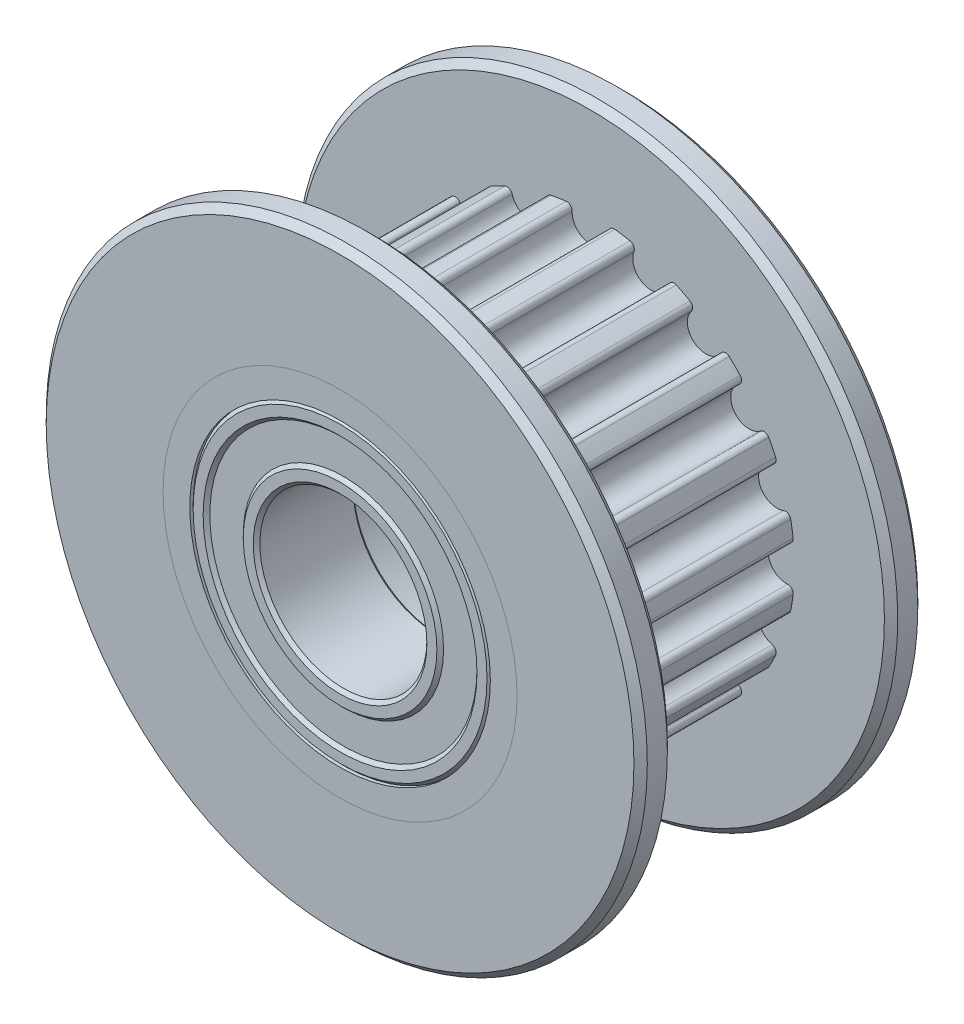
SolidWorks part; units mm, degrees
ref_plane "Přední rovina" through (0, 0, 0) normal (0, 0, 1) x (1, 0, 0)
ref_plane "Horní rovina" through (0, 0, 0) normal (0, 1, 0) x (1, 0, 0)
ref_plane "Pravá rovina" through (0, 0, 0) normal (1, 0, 0) x (0, 0, -1)
sketch "Skica1" plane through (0, 0, 0) normal (0, 0, 1) x (1, 0, 0)
  circle A0 centre (0, 0) radius 5.3
  circle A1 centre (0, 0) radius 4
  circle A2 centre (0, 0) radius 9
  dimension "D1" = 10.6
  dimension "D2" = 8
  dimension "D3" = 18
extrude "Přidat vysunutím1" add sketch "Skica1" along normal blind 8.5 contours A0 A1 region at (-5.1501, 0, 0)
extrude "Přidat vysunutím2" add sketch "Skica1<3>" along normal blind 1 separate body contours A2 A0 region at (-8.7454, 0, 0)
sketch "Skica1<3>" plane through (0, 0, 0) normal (0, 0, 1) x (1, 0, 0) same geometry as "Skica1"
sketch "Skica2" plane through (0, 0, 1) normal (0, 0, 1) x (1, 0, 0)
  arc A2 (-0.5492, 5.8991) -> (0.5492, 5.8991) centre (0, 5.87) ccw
  arc A3 (-0.5492, 5.8991) -> (-0.7281, 6.0665) centre (-0.709, 5.9076) ccw
  arc A4 (0.7281, 6.0665) -> (0.5492, 5.8991) centre (0.709, 5.9076) ccw
  arc A5 (1.1822, 5.9945) -> (0.7281, 6.0665) centre (0, 0) ccw
  arc A6 (1.3006, 5.7801) -> (2.3453, 5.4407) centre (1.8139, 5.5827) ccw
  arc A7 (1.3006, 5.7801) -> (1.1822, 5.9945) centre (1.1512, 5.8376) ccw
  arc A8 (2.5671, 5.5446) -> (2.3453, 5.4407) centre (2.4999, 5.3994) ccw
  arc A9 (2.9768, 5.3358) -> (2.5671, 5.5446) centre (0, 0) ccw
  arc A10 (3.0231, 5.0953) -> (3.9118, 4.4497) centre (3.4503, 4.7489) ccw
  arc A11 (3.0231, 5.0953) -> (2.9768, 5.3358) centre (2.8988, 5.1961) ccw
  arc A12 (4.1548, 4.4799) -> (3.9118, 4.4497) centre (4.046, 4.3626) ccw
  arc A13 (4.4799, 4.1548) -> (4.1548, 4.4799) centre (0, 0) ccw
  arc A14 (4.4497, 3.9118) -> (5.0953, 3.0231) centre (4.7489, 3.4503) ccw
  arc A15 (4.4497, 3.9118) -> (4.4799, 4.1548) centre (4.3626, 4.046) ccw
  arc A16 (5.3358, 2.9768) -> (5.0953, 3.0231) centre (5.1961, 2.8988) ccw
  arc A17 (5.5446, 2.5671) -> (5.3358, 2.9768) centre (0, 0) ccw
  arc A18 (5.4407, 2.3453) -> (5.7801, 1.3006) centre (5.5827, 1.8139) ccw
  arc A19 (5.4407, 2.3453) -> (5.5446, 2.5671) centre (5.3994, 2.4999) ccw
  arc A20 (5.9945, 1.1822) -> (5.7801, 1.3006) centre (5.8376, 1.1512) ccw
  arc A21 (6.0665, 0.7281) -> (5.9945, 1.1822) centre (0, 0) ccw
  arc A22 (5.8991, 0.5492) -> (5.8991, -0.5492) centre (5.87, 0) ccw
  arc A23 (5.8991, 0.5492) -> (6.0665, 0.7281) centre (5.9076, 0.709) ccw
  arc A24 (6.0665, -0.7281) -> (5.8991, -0.5492) centre (5.9076, -0.709) ccw
  arc A25 (5.9945, -1.1822) -> (6.0665, -0.7281) centre (0, 0) ccw
  arc A26 (5.7801, -1.3006) -> (5.4407, -2.3453) centre (5.5827, -1.8139) ccw
  arc A27 (5.7801, -1.3006) -> (5.9945, -1.1822) centre (5.8376, -1.1512) ccw
  arc A28 (5.5446, -2.5671) -> (5.4407, -2.3453) centre (5.3994, -2.4999) ccw
  arc A29 (5.3358, -2.9768) -> (5.5446, -2.5671) centre (0, 0) ccw
  arc A30 (5.0953, -3.0231) -> (4.4497, -3.9118) centre (4.7489, -3.4503) ccw
  arc A31 (5.0953, -3.0231) -> (5.3358, -2.9768) centre (5.1961, -2.8988) ccw
  arc A32 (4.4799, -4.1548) -> (4.4497, -3.9118) centre (4.3626, -4.046) ccw
  arc A33 (4.1548, -4.4799) -> (4.4799, -4.1548) centre (0, 0) ccw
  arc A34 (3.9118, -4.4497) -> (3.0231, -5.0953) centre (3.4503, -4.7489) ccw
  arc A35 (3.9118, -4.4497) -> (4.1548, -4.4799) centre (4.046, -4.3626) ccw
  arc A36 (2.9768, -5.3358) -> (3.0231, -5.0953) centre (2.8988, -5.1961) ccw
  arc A37 (2.5671, -5.5446) -> (2.9768, -5.3358) centre (0, 0) ccw
  arc A38 (2.3453, -5.4407) -> (1.3006, -5.7801) centre (1.8139, -5.5827) ccw
  arc A39 (2.3453, -5.4407) -> (2.5671, -5.5446) centre (2.4999, -5.3994) ccw
  arc A40 (1.1822, -5.9945) -> (1.3006, -5.7801) centre (1.1512, -5.8376) ccw
  arc A41 (0.7281, -6.0665) -> (1.1822, -5.9945) centre (0, 0) ccw
  arc A42 (0.5492, -5.8991) -> (-0.5492, -5.8991) centre (0, -5.87) ccw
  arc A43 (0.5492, -5.8991) -> (0.7281, -6.0665) centre (0.709, -5.9076) ccw
  arc A44 (-0.7281, -6.0665) -> (-0.5492, -5.8991) centre (-0.709, -5.9076) ccw
  arc A45 (-1.1822, -5.9945) -> (-0.7281, -6.0665) centre (0, 0) ccw
  arc A46 (-1.3006, -5.7801) -> (-2.3453, -5.4407) centre (-1.8139, -5.5827) ccw
  arc A47 (-1.3006, -5.7801) -> (-1.1822, -5.9945) centre (-1.1512, -5.8376) ccw
  arc A48 (-2.5671, -5.5446) -> (-2.3453, -5.4407) centre (-2.4999, -5.3994) ccw
  arc A49 (-2.9768, -5.3358) -> (-2.5671, -5.5446) centre (0, 0) ccw
  arc A50 (-3.0231, -5.0953) -> (-3.9118, -4.4497) centre (-3.4503, -4.7489) ccw
  arc A51 (-3.0231, -5.0953) -> (-2.9768, -5.3358) centre (-2.8988, -5.1961) ccw
  arc A52 (-4.1548, -4.4799) -> (-3.9118, -4.4497) centre (-4.046, -4.3626) ccw
  arc A53 (-4.4799, -4.1548) -> (-4.1548, -4.4799) centre (0, 0) ccw
  arc A54 (-4.4497, -3.9118) -> (-5.0953, -3.0231) centre (-4.7489, -3.4503) ccw
  arc A55 (-4.4497, -3.9118) -> (-4.4799, -4.1548) centre (-4.3626, -4.046) ccw
  arc A56 (-5.3358, -2.9768) -> (-5.0953, -3.0231) centre (-5.1961, -2.8988) ccw
  arc A57 (-5.5446, -2.5671) -> (-5.3358, -2.9768) centre (0, 0) ccw
  arc A58 (-5.4407, -2.3453) -> (-5.7801, -1.3006) centre (-5.5827, -1.8139) ccw
  arc A59 (-5.4407, -2.3453) -> (-5.5446, -2.5671) centre (-5.3994, -2.4999) ccw
  arc A60 (-5.9945, -1.1822) -> (-5.7801, -1.3006) centre (-5.8376, -1.1512) ccw
  arc A61 (-6.0665, -0.7281) -> (-5.9945, -1.1822) centre (0, 0) ccw
  arc A62 (-5.8991, -0.5492) -> (-5.8991, 0.5492) centre (-5.87, 0) ccw
  arc A63 (-5.8991, -0.5492) -> (-6.0665, -0.7281) centre (-5.9076, -0.709) ccw
  arc A64 (-6.0665, 0.7281) -> (-5.8991, 0.5492) centre (-5.9076, 0.709) ccw
  arc A65 (-5.9945, 1.1822) -> (-6.0665, 0.7281) centre (0, 0) ccw
  arc A66 (-5.7801, 1.3006) -> (-5.4407, 2.3453) centre (-5.5827, 1.8139) ccw
  arc A67 (-5.7801, 1.3006) -> (-5.9945, 1.1822) centre (-5.8376, 1.1512) ccw
  arc A68 (-5.5446, 2.5671) -> (-5.4407, 2.3453) centre (-5.3994, 2.4999) ccw
  arc A69 (-5.3358, 2.9768) -> (-5.5446, 2.5671) centre (0, 0) ccw
  arc A70 (-5.0953, 3.0231) -> (-4.4497, 3.9118) centre (-4.7489, 3.4503) ccw
  arc A71 (-5.0953, 3.0231) -> (-5.3358, 2.9768) centre (-5.1961, 2.8988) ccw
  arc A72 (-4.4799, 4.1548) -> (-4.4497, 3.9118) centre (-4.3626, 4.046) ccw
  arc A73 (-4.1548, 4.4799) -> (-4.4799, 4.1548) centre (0, 0) ccw
  arc A74 (-3.9118, 4.4497) -> (-3.0231, 5.0953) centre (-3.4503, 4.7489) ccw
  arc A75 (-3.9118, 4.4497) -> (-4.1548, 4.4799) centre (-4.046, 4.3626) ccw
  arc A76 (-2.9768, 5.3358) -> (-3.0231, 5.0953) centre (-2.8988, 5.1961) ccw
  arc A77 (-2.5671, 5.5446) -> (-2.9768, 5.3358) centre (0, 0) ccw
  arc A78 (-2.3453, 5.4407) -> (-1.3006, 5.7801) centre (-1.8139, 5.5827) ccw
  arc A79 (-2.3453, 5.4407) -> (-2.5671, 5.5446) centre (-2.4999, 5.3994) ccw
  arc A80 (-1.1822, 5.9945) -> (-1.3006, 5.7801) centre (-1.1512, 5.8376) ccw
  arc A81 (-0.7281, 6.0665) -> (-1.1822, 5.9945) centre (0, 0) ccw
  circle A82 centre (0, 0) radius 5.3
  point P5 (0, 0)
  point P145 (0, 0)
extrude "Přidat vysunutím5" add sketch "Skica2" along normal blind 6.5 separate body
sketch "Skica4" plane through (0, 0, 7.5) normal (0, 0, 1) x (1, 0, 0)
  circle A0 centre (0, 0) radius 9
  circle A1 centre (0, 0) radius 5.3
extrude "Přidat vysunutím6" add sketch "Skica4" along normal blind 1 separate body
sketch "Skica5" plane through (0, 0, 8.5) normal (0, 0, 1) x (1, 0, 0)
  circle A0 centre (0, 0) radius 4.5
  dimension "D1" = 9
sketch "Skica6" plane through (0, 0, 0) normal (0, 0, -1) x (-1, 0, 0)
  circle A0 centre (0, 0) radius 4.5
  dimension "D1" = 9
extrude "Odebrat vysunutím3" cut sketch "Skica5" against normal blind 3
extrude "Odebrat vysunutím4" cut sketch "Skica6" against normal blind 3
chamfer "Zkosení1" distance 0.2 angle 45 2 edges at (9, 0, 1) (9, 0, 0)
chamfer "Zkosení2" distance 0.2 angle 45 2 edges at (9, 0, 7.5) (9, 0, 8.5)
sketch "Skica7" plane through (0, 0, 3) normal (0, 0, -1) x (-1, 0, 0)
  circle A0 centre (0, 0) radius 4.5
  circle A1 centre (0, 0) radius 2.5
  circle A2 centre (0, 0) radius 3
  circle A3 centre (0, 0) radius 4
  circle M1 centre (0, 0) radius 4
  circle M2 centre (0, 0) radius 4.5
extrude "Přidat vysunutím7" add sketch "Skica7" along normal blind 3 separate body contours M2 M1 | A2 A1 region at (4.3727, 0, 3) region at (2.9151, 0, 3)
extrude "Přidat vysunutím8" add sketch "Skica7<3>" along normal blind 2.8 from offset 0.1 separate body contours A2 M1 region at (3.8869, 0, 3)
sketch "Skica7<3>" plane through (0, 0, 3) normal (0, 0, -1) x (-1, 0, 0) same geometry as "Skica7"
chamfer "Zkosení3" distance 0.1 angle 45 2 edges at (-4, 0, 0) (-4.5, 0, 0)
chamfer "Zkosení4" distance 0.1 angle 45 2 edges at (-3, 0, 0) (-2.5, 0, 0)
sketch "Skica8" plane through (0, 0, 5.5) normal (0, 0, 1) x (1, 0, 0)
  circle A0 centre (0, 0) radius 4.5
  circle A1 centre (0, 0) radius 2.5
  circle A2 centre (0, 0) radius 3
  circle A3 centre (0, 0) radius 4
  circle M1 centre (0, 0) radius 4
  circle M2 centre (0, 0) radius 4.5
  dimension "D1" = 9
  dimension "D2" = 8
  dimension "D3" = 6
  dimension "D4" = 5
extrude "Přidat vysunutím9" add sketch "Skica8" along normal blind 3 separate body contours M2 M1 | A2 A1 region at (-4.3727, 0, 5.5) region at (-2.9151, 0, 5.5)
extrude "Přidat vysunutím10" add sketch "Skica8<3>" along normal blind 2.8 from offset 0.1 separate body contours A2 M1 region at (-3.8869, 0, 5.5)
sketch "Skica8<3>" plane through (0, 0, 5.5) normal (0, 0, 1) x (1, 0, 0) same geometry as "Skica8"
chamfer "Zkosení5" distance 0.1 angle 45 2 edges at (4, 0, 8.5) (4.5, 0, 8.5)
chamfer "Zkosení6" distance 0.1 angle 45 2 edges at (3, 0, 8.5) (2.5, 0, 8.5)
chamfer "Zkosení7" distance 0.1 angle 45 2 edges at (3, 0, 5.5) (2.5, 0, 5.5)
chamfer "Zkosení8" distance 0.1 angle 45 2 edges at (4.5, 0, 5.5) (4, 0, 5.5)
chamfer "Zkosení10" distance 0.1 angle 45 2 edges at (-3, 0, 3) (-2.5, 0, 3)
chamfer "Zkosení12" distance 0.1 angle 45 2 edges at (-4, 0, 3) (-4.5, 0, 3)
